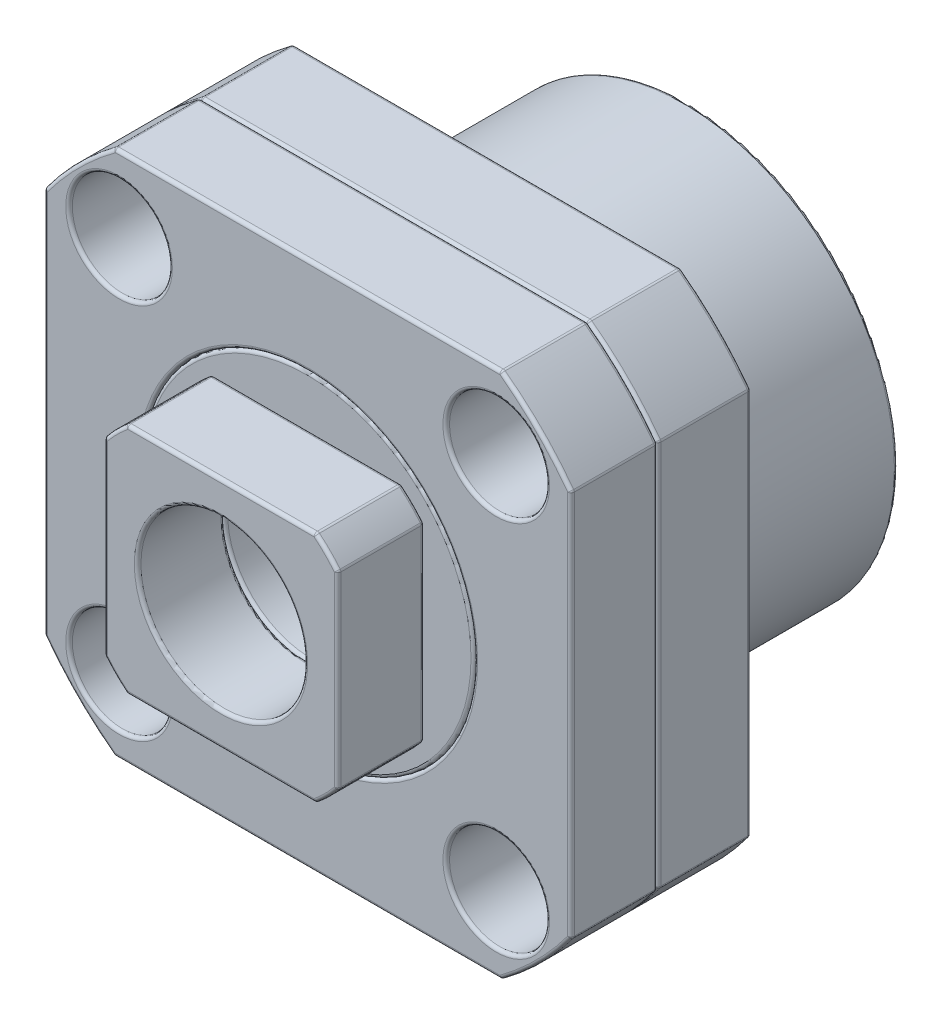
SolidWorks part; units mm, degrees
ref_plane "Front Plane" through (0, 0, 0) normal (0, 0, 1) x (1, 0, 0)
ref_plane "Top Plane" through (0, 0, 0) normal (0, 1, 0) x (1, 0, 0)
ref_plane "Right Plane" through (0, 0, 0) normal (1, 0, 0) x (0, 0, -1)
sketch "Sketch1" plane through (0, 0, 0) normal (0, 0, 1) x (1, 0, 0)
  line L0 (0, -39.5) -> (0, 39.5) construction
  line L1 (-39.5, 0) -> (39.5, 0) construction
  line L2 (-39.5, -39.5) -> (39.5, 39.5) construction
  line L3 (-39.5, 39.5) -> (39.5, 39.5)
  line L4 (-39.5, 39.5) -> (-39.5, -39.5)
  line L5 (-39.5, -39.5) -> (39.5, -39.5)
  line L6 (39.5, 39.5) -> (39.5, -39.5)
  line L7 (-39.5, 39.5) -> (39.5, -39.5) construction
  circle A0 centre (0, 0) radius 40 construction
  circle A1 centre (-28.2843, -28.2843) radius 7.5
  circle A2 centre (28.2843, -28.2843) radius 7.5
  circle A3 centre (28.2843, 28.2843) radius 7.5
  circle A4 centre (-28.2843, 28.2843) radius 7.5
  point P4 (0, 0)
  point P8 (0, 0)
  dimension "PCD" = 80
  dimension "d2" = 15
  dimension "B" = 79
  dimension "D1" = 79
extrude "Boss-Extrude1" add sketch "Sketch1" along normal blind 13
sketch "Sketch2" plane through (0, 0, 0) normal (0, 0, 1) x (1, 0, 0)
  circle A0 centre (0, 0) radius 49
  dimension "A" = 98
extrude "Cut-Extrude2" cut sketch "Sketch2" along normal blind 13 flip side to cut
sketch "Sketch3" plane through (0, 0, 0) normal (0, 0, 1) x (1, 0, 0)
  circle A0 centre (0, 0) radius 26
  dimension "Bearing outside diameter" = 52
extrude "Boss-Extrude2" add sketch "Sketch3" against normal blind 1
sketch "Sketch4" plane through (0, 0, 13) normal (0, 0, 1) x (1, 0, 0)
  circle A0 centre (0, 0) radius 25
  dimension "D1" = 50
extrude "Cut-Extrude3" cut sketch "Sketch4" against normal blind 14
sketch "Sketch5" plane through (0, 0, 13) normal (0, 0, 1) x (1, 0, 0)
  circle A0 centre (0, 0) radius 25
  circle A1 centre (0, 0) radius 12.5
  dimension "D1" = 25
  dimension "D2" = 50
extrude "Boss-Extrude4" add sketch "Sketch5" against normal blind 14 separate body
fillet "Fillet1" radius 0.5 4 edges at (25, 0, 13) (12.5, 0, 13) (12.5, 0, -1) (25, 0, -1)
sketch "Sketch6" plane through (0, 0, 0) normal (0, 0, 1) x (1, 0, 0)
  line L0 (-39.5, 0) -> (39.5, 0) construction
  line L2 (0, -39.5) -> (0, 39.5) construction
  line L3 (28.9957, 39.5) -> (-28.9957, 39.5) construction
  line L4 (-39.5, 39.5) -> (39.5, 39.5)
  line L5 (39.5, 39.5) -> (39.5, -39.5)
  line L6 (39.5, -39.5) -> (-39.5, -39.5)
  line L7 (-39.5, -39.5) -> (-39.5, 39.5)
  line L8 (0, 39.5) -> (0, 24.886) construction
  line L9 (-13.5, 24.886) -> (13.5, 24.886) construction
  circle A0 centre (0, 0) radius 26
  circle A1 centre (-28.2843, 28.2843) radius 4.5
  circle A2 centre (28.2843, 28.2843) radius 4.5
  circle A3 centre (28.2843, -28.2843) radius 4.5
  circle A4 centre (-28.2843, -28.2843) radius 4.5
  point P8 (0, 0)
  point P14 (0, 0)
  point P24 (0, 24.886)
  dimension "D1" = 52
  dimension "d11" = 9
  dimension "H" = 27
  dimension "D2" = 79
extrude "Boss-Extrude5" add sketch "Sketch6" against normal blind 14 separate body
sketch "Sketch7" plane through (0, 0, 0) normal (0, 0, 1) x (1, 0, 0)
  circle A0 centre (0, 0) radius 49
  dimension "D1" = 98
extrude "Cut-Extrude5" cut sketch "Sketch7" against normal blind 14 flip side to cut
sketch "Sketch8" plane through (0, 0, -14) normal (0, 0, 1) x (1, 0, 0)
  circle A0 centre (0, 0) radius 31.5
  circle A1 centre (0, 0) radius 26
  dimension "D" = 63
  dimension "D2" = 52
extrude "Boss-Extrude6" add sketch "Sketch8" against normal blind 30
sketch "Sketch10" plane through (0, 0, -44) normal (0, 0, 1) x (1, 0, 0)
  circle A0 centre (0, 0) radius 26
  circle A1 centre (0, 0) radius 25
  dimension "D2" = 50
  dimension "D1" = 52
extrude "Boss-Extrude7" add sketch "Sketch10" along normal blind 10
sketch "Sketch11" plane through (0, 0, -1) normal (0, 0, 1) x (1, 0, 0)
  circle A0 centre (0, 0) radius 26
  circle A1 centre (0, 0) radius 12.5
  dimension "D1" = 52
  dimension "D2" = 25
extrude "Boss-Extrude8" add sketch "Sketch11" against normal blind 30 separate body
fillet "Fillet2" radius 0.5 2 edges at (12.5, 0, -1) (12.5, 0, -31)
sketch "Sketch12" plane through (0, 0, -44) normal (0, 0, 1) x (1, 0, 0)
  circle A0 centre (0, 0) radius 25
  circle A1 centre (0, 0) radius 12.5
  dimension "D1" = 50
  dimension "D2" = 25
extrude "Boss-Extrude9" add sketch "Sketch12" along normal blind 14 separate body
fillet "Fillet3" radius 0.5 3 edges at (25, 0, -44) (12.5, 0, -44) (12.5, 0, -30)
fillet "Fillet4" radius 0.5 27 edges at (25, 0, -44) (31.5, 0, -44) (-31.5, 0, -14) (-34.6482, 34.6482, -14) (-34.6482, 34.6482, 0) (-39.5, 28.9957, -7) (-39.5, 0, 0) (-39.5, 0, -14) (-39.5, -28.9957, -7) (-34.6482, -34.6482, 0) (-34.6482, -34.6482, -14) (-28.9957, -39.5, -7) (0, -39.5, 0) (0, -39.5, -14) (34.6482, -34.6482, -14) (28.9957, -39.5, -7) (34.6482, -34.6482, 0) (39.5, -28.9957, -7) (39.5, 0, 0) (39.5, 0, -14) (0, 39.5, 0) (-28.9957, 39.5, -7) (0, 39.5, -14) (28.9957, 39.5, -7) (34.6482, 34.6482, -14) (39.5, 28.9957, -7) (34.6482, 34.6482, 0)
sketch "Sketch13" plane through (0, 0, 13) normal (0, 0, 1) x (1, 0, 0)
  line L0 (0, -17.5) -> (0, 17.5) construction
  line L1 (-17.5, 0) -> (17.5, 0) construction
  line L2 (-17.5, 17.5) -> (17.5, 17.5)
  line L3 (17.5, 17.5) -> (17.5, -17.5)
  line L4 (17.5, -17.5) -> (-17.5, -17.5)
  line L5 (-17.5, -17.5) -> (-17.5, 17.5)
  point P5 (0, 0)
  point P10 (0, 0)
  dimension "D1" = 35
  dimension "T" = 35
extrude "Boss-Extrude10" add sketch "Sketch13" along normal blind 13 separate body
sketch "Sketch14" plane through (0, 0, 26) normal (0, 0, 1) x (1, 0, 0)
  circle A0 centre (0, 0) radius 22.5
  dimension "D1" = 45
extrude "Cut-Extrude6" cut sketch "Sketch14" against normal blind 13 flip side to cut
sketch "Sketch15" plane through (0, 0, 26) normal (0, 0, 1) x (1, 0, 0)
  circle A0 centre (0, 0) radius 12.5
  dimension "D1" = 25
extrude "Cut-Extrude7" cut sketch "Sketch15" against normal blind 13
fillet "Fillet5" radius 0.5 26 edges at (12.5, 0, 26) (12.5, 0, 13) (15.9099, 15.9099, 26) (15.9099, 15.9099, 13) (17.5, 0, 26) (17.5, 14.1421, 19.5) (17.5, 0, 13) (15.9099, -15.9099, 26) (17.5, -14.1421, 19.5) (15.9099, -15.9099, 13) (0, -17.5, 26) (14.1421, -17.5, 19.5) (0, -17.5, 13) (-15.9099, -15.9099, 26) (-14.1421, -17.5, 19.5) (-15.9099, -15.9099, 13) (-17.5, 0, 26) (-17.5, -14.1421, 19.5) (-17.5, 0, 13) (0, 17.5, 26) (0, 17.5, 13) (14.1421, 17.5, 19.5) (-15.9099, 15.9099, 13) (-14.1421, 17.5, 19.5) (-15.9099, 15.9099, 26) (-17.5, 14.1421, 19.5)
fillet "Fillet6" radius 0.5 29 edges at (-20.7843, 28.2843, 13) (35.7843, -28.2843, 13) (-20.7843, -28.2843, 13) (35.7843, 28.2843, 13) (25, 0, 13) (-34.6482, 34.6482, 0) (-34.6482, 34.6482, 13) (-39.5, 28.9957, 6.5) (-39.5, 0, 13) (-39.5, 0, 0) (-39.5, -28.9957, 6.5) (-34.6482, -34.6482, 13) (-34.6482, -34.6482, 0) (-28.9957, -39.5, 6.5) (0, -39.5, 13) (0, -39.5, 0) (28.9957, -39.5, 6.5) (34.6482, -34.6482, 13) (34.6482, -34.6482, 0) (39.5, -28.9957, 6.5) (39.5, 0, 13) (39.5, 0, 0) (39.5, 28.9957, 6.5) (34.6482, 34.6482, 13) (34.6482, 34.6482, 0) (28.9957, 39.5, 6.5) (0, 39.5, 13) (-28.9957, 39.5, 6.5) (0, 39.5, 0)
equation "\"D1@Sketch1\"=\"B@Sketch1\""
equation "\"D1@Cut-Extrude2\" = \"h@Boss-Extrude1\""
equation "\"D1@Cut-Extrude3\"=\"h@Boss-Extrude1\"+\"D1@Boss-Extrude2\""
equation "\"D2@Sketch5\"=\"D1@Sketch4\""
equation "\"D1@Boss-Extrude4\"=\"D1@Cut-Extrude3\""
equation "\"D1@Sketch4\"=\"Bearing outside diameter@Sketch3\"-2"
equation "\"D1@Sketch6\"=\"Bearing outside diameter@Sketch3\""
equation "\"D1@Boss-Extrude5\"=\"H@Sketch6\"-\"h@Boss-Extrude1\""
equation "\"D1@Sketch7\"=\"A@Sketch2\""
equation "\"D1@Cut-Extrude5\"=\"D1@Boss-Extrude5\""
equation "\"D2@Sketch8\"=\"Bearing outside diameter@Sketch3\""
equation "\"D1@Sketch10\"=\"Bearing outside diameter@Sketch3\""
equation "\"D2@Sketch10\"=\"D2@Sketch5\""
equation "\"D1@Sketch11\"=\"Bearing outside diameter@Sketch3\""
equation "\"D1@Boss-Extrude8\" = \"F@Boss-Extrude6\""
equation "\"D2@Sketch11\"=\"D1@Sketch5\""
equation "\"D1@Sketch12\"=\"D2@Sketch5\""
equation "\"D2@Sketch12\"=\"D1@Sketch5\""
equation "\"D1@Boss-Extrude9\"=\"D1@Boss-Extrude4\""
equation "\"D1@Sketch13\"=\"T@Sketch13\""
equation "\"D1@Sketch14\"=\"D2@Sketch5\"-5"
equation "\"D1@Cut-Extrude6\"=\"L1@Boss-Extrude10\""
equation "\"D1@Sketch15\"=\"D1@Sketch5\""
equation "\"D1@Cut-Extrude7\"=\"L1@Boss-Extrude10\""
equation "\"D2@Sketch6\"=\"B@Sketch1\""
